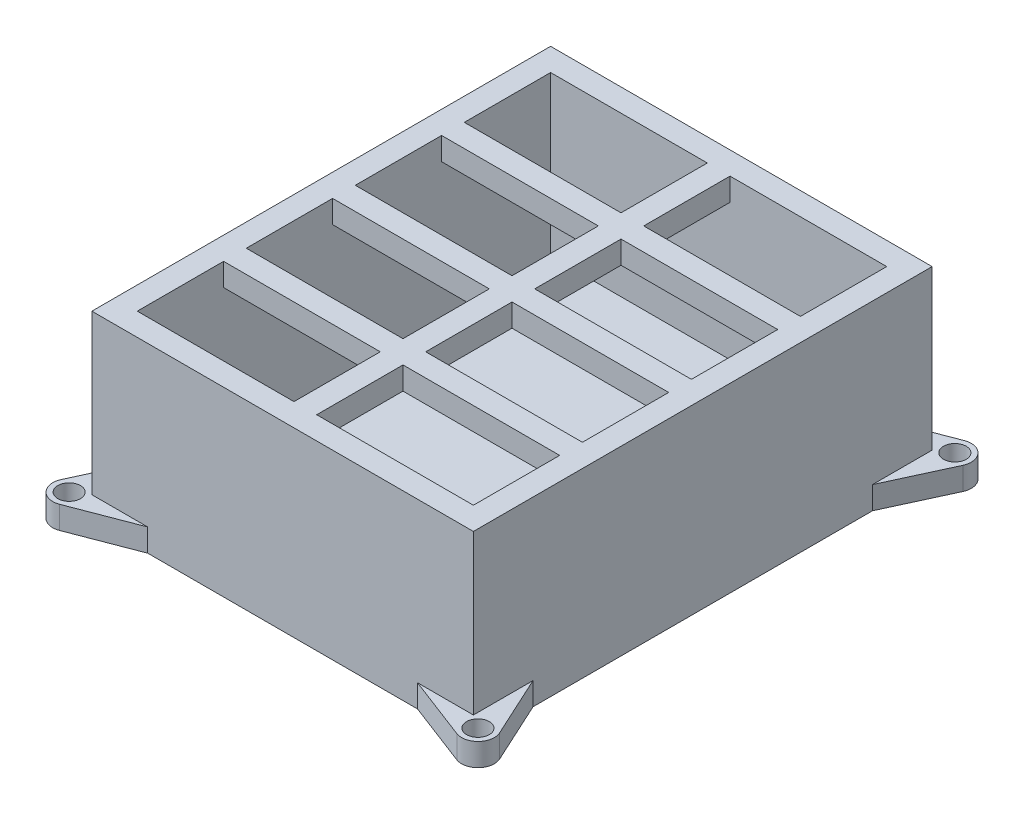
SolidWorks part; units mm, degrees
ref_plane "Front Plane" through (0, 0, 0) normal (0, 0, 1) x (1, 0, 0)
ref_plane "Top Plane" through (0, 0, 0) normal (0, 1, 0) x (1, 0, 0)
ref_plane "Right Plane" through (0, 0, 0) normal (1, 0, 0) x (0, 0, -1)
sketch "Sketch1" plane through (0, 0, 0) normal (0, 1, 0) x (1, 0, 0)
  line L0 (0, 0) -> (0, 10.1) construction
  line L1 (-8.4, -10.1) -> (8.4, -10.1)
  line L2 (-8.4, -10.1) -> (-8.4, 10.1)
  line L3 (-8.4, 10.1) -> (8.4, 10.1)
  line L4 (8.4, -10.1) -> (8.4, 10.1)
  line L5 (-8.4, -10.1) -> (8.4, 10.1) construction
  line L6 (-8.4, 10.1) -> (8.4, -10.1) construction
  line L7 (0, 0) -> (8.4, 0) construction
  line L9 (-7.4, -5.3) -> (-0.5, -5.3)
  line L10 (-7.4, -5.3) -> (-7.4, -9.1)
  line L11 (-7.4, -9.1) -> (-0.5, -9.1)
  line L12 (-0.5, -5.3) -> (-0.5, -9.1)
  line L16 (7.4, -9.1) -> (0.5, -9.1)
  line L17 (0.5, -5.3) -> (0.5, -9.1)
  line L18 (7.4, -5.3) -> (0.5, -5.3)
  line L19 (7.4, -5.3) -> (7.4, -9.1)
  line L20 (-7.4, -0.5) -> (-7.4, -4.3)
  line L21 (-7.4, -0.5) -> (-0.5, -0.5)
  line L22 (-0.5, -0.5) -> (-0.5, -4.3)
  line L23 (-7.4, -4.3) -> (-0.5, -4.3)
  line L24 (7.4, -4.3) -> (0.5, -4.3)
  line L25 (0.5, -0.5) -> (0.5, -4.3)
  line L26 (7.4, -0.5) -> (0.5, -0.5)
  line L27 (7.4, -0.5) -> (7.4, -4.3)
  line L44 (7.4, 0.5) -> (7.4, 4.3)
  line L45 (7.4, 0.5) -> (0.5, 0.5)
  line L46 (0.5, 0.5) -> (0.5, 4.3)
  line L47 (7.4, 4.3) -> (0.5, 4.3)
  line L48 (7.4, 5.3) -> (7.4, 9.1)
  line L49 (7.4, 5.3) -> (0.5, 5.3)
  line L50 (0.5, 5.3) -> (0.5, 9.1)
  line L51 (7.4, 9.1) -> (0.5, 9.1)
  line L52 (-7.4, 9.1) -> (-0.5, 9.1)
  line L53 (-0.5, 5.3) -> (-0.5, 9.1)
  line L54 (-7.4, 5.3) -> (-0.5, 5.3)
  line L55 (-7.4, 5.3) -> (-7.4, 9.1)
  line L56 (-7.4, 0.5) -> (-0.5, 0.5)
  line L57 (-0.5, 0.5) -> (-0.5, 4.3)
  line L58 (-7.4, 4.3) -> (-0.5, 4.3)
  line L59 (-7.4, 0.5) -> (-7.4, 4.3)
  point P0 (0, 0)
  point P43 (-3.95, 9.1)
  dimension "D1" = 6.9
  dimension "D2" = 3.8
  dimension "D4" = 1
  dimension "D5" = 1
  dimension "D6" = 1
  dimension "D7" = 1
  dimension "D8" = 1
  dimension "D3" = 2
extrude "Boss-Extrude1" add sketch "Sketch1" along normal blind 1 contours L1 L4 L3 L2 L51 L48 L49 L50 L47 L44 L45 L46 L23 L20 L21 L22 L9 L12 L11 L10 L18 L19 L16 L17 L26 L27 L24 L25 L54 L55 L52 L53 L56 L59 L58 L57 | L59 L56 L57 L58 | L55 L54 L53 L52 | L48 L51 L50 L49 | L44 L47 L46 L45 | L27 L26 L25 L24 | L20 L23 L22 L21 | L12 L9 L10 L11 | L19 L18 L17 L16 region at (0, 0, 0) region at (-3.95, 0, 7.2) region at (3.95, 0, 7.2) region at (-3.95, 0, 2.4) region at (3.95, 0, 2.4) region at (3.95, 0, -2.4) region at (3.95, 0, -7.2) region at (-3.95, 0, -7.2) region at (-3.95, 0, -2.4)
ref_plane "Plane1" through (0, 7, 0) normal (0, 1, 0) x (1, 0, 0)
sketch "Sketch2" plane through (0, 7, 0) normal (0, 1, 0) x (1, 0, 0)
  line L0 (-7.4, -5.3) -> (-7.4, -9.1) construction
  line L1 (-7.4, -5.3) -> (-0.5, -5.3) construction
  line L2 (-0.5, -5.3) -> (-0.5, -9.1) construction
  line L3 (-7.4, -9.1) -> (-0.5, -9.1) construction
  line L4 (-8.4, -10.1) -> (8.4, -10.1)
  line L6 (-8.4, -10.1) -> (8.4, -10.1)
  line L12 (7.4, -9.1) -> (0.5, -9.1) construction
  line L13 (7.4, -5.3) -> (7.4, -9.1) construction
  line L14 (0.5, -5.3) -> (0.5, -9.1) construction
  line L15 (7.4, -5.3) -> (0.5, -5.3) construction
  line L16 (7.4, -0.5) -> (7.4, -4.3) construction
  line L17 (7.4, -0.5) -> (0.5, -0.5) construction
  line L18 (7.4, -4.3) -> (0.5, -4.3) construction
  line L19 (0.5, -0.5) -> (0.5, -4.3) construction
  line L20 (-0.5, -0.5) -> (-0.5, -4.3) construction
  line L21 (-7.4, -4.3) -> (-0.5, -4.3) construction
  line L22 (-7.4, -0.5) -> (-7.4, -4.3) construction
  line L23 (-7.4, -0.5) -> (-0.5, -0.5) construction
  line L24 (-0.5, 0.5) -> (-0.5, 4.3) construction
  line L25 (-7.4, 4.3) -> (-0.5, 4.3) construction
  line L26 (-7.4, 0.5) -> (-7.4, 4.3) construction
  line L27 (-7.4, 0.5) -> (-0.5, 0.5) construction
  line L28 (7.4, 0.5) -> (7.4, 4.3) construction
  line L29 (7.4, 0.5) -> (0.5, 0.5) construction
  line L30 (0.5, 0.5) -> (0.5, 4.3) construction
  line L31 (7.4, 4.3) -> (0.5, 4.3) construction
  line L32 (7.4, 5.3) -> (7.4, 9.1) construction
  line L33 (7.4, 9.1) -> (0.5, 9.1) construction
  line L34 (7.4, 5.3) -> (0.5, 5.3) construction
  line L35 (0.5, 5.3) -> (0.5, 9.1) construction
  line L36 (-0.5, 5.3) -> (-0.5, 9.1) construction
  line L37 (-7.4, 5.3) -> (-0.5, 5.3) construction
  line L38 (-7.4, 5.3) -> (-7.4, 9.1) construction
  line L39 (-7.4, 9.1) -> (-0.5, 9.1) construction
  line L40 (-7.4, -5.3) -> (-7.4, -9.1)
  line L41 (-7.4, -5.3) -> (-0.5, -5.3)
  line L42 (-0.5, -5.3) -> (-0.5, -9.1)
  line L43 (-7.4, -9.1) -> (-0.5, -9.1)
  line L44 (7.4, -9.1) -> (0.5, -9.1)
  line L45 (7.4, -5.3) -> (7.4, -9.1)
  line L46 (0.5, -5.3) -> (0.5, -9.1)
  line L47 (7.4, -5.3) -> (0.5, -5.3)
  line L48 (7.4, -0.5) -> (7.4, -4.3)
  line L49 (7.4, -0.5) -> (0.5, -0.5)
  line L50 (7.4, -4.3) -> (0.5, -4.3)
  line L51 (0.5, -0.5) -> (0.5, -4.3)
  line L52 (-0.5, -0.5) -> (-0.5, -4.3)
  line L53 (-7.4, -4.3) -> (-0.5, -4.3)
  line L54 (-7.4, -0.5) -> (-7.4, -4.3)
  line L55 (-7.4, -0.5) -> (-0.5, -0.5)
  line L56 (-0.5, 0.5) -> (-0.5, 4.3)
  line L57 (-7.4, 4.3) -> (-0.5, 4.3)
  line L58 (-7.4, 0.5) -> (-7.4, 4.3)
  line L59 (-7.4, 0.5) -> (-0.5, 0.5)
  line L60 (7.4, 0.5) -> (7.4, 4.3)
  line L61 (7.4, 0.5) -> (0.5, 0.5)
  line L62 (0.5, 0.5) -> (0.5, 4.3)
  line L63 (7.4, 4.3) -> (0.5, 4.3)
  line L64 (7.4, 5.3) -> (7.4, 9.1)
  line L65 (7.4, 9.1) -> (0.5, 9.1)
  line L66 (7.4, 5.3) -> (0.5, 5.3)
  line L67 (0.5, 5.3) -> (0.5, 9.1)
  line L68 (-0.5, 5.3) -> (-0.5, 9.1)
  line L69 (-7.4, 5.3) -> (-0.5, 5.3)
  line L70 (-7.4, 5.3) -> (-7.4, 9.1)
  line L71 (-7.4, 9.1) -> (-0.5, 9.1)
  line L76 (8.4, -10.1) -> (8.4, 10.1)
  line L78 (8.4, -10.1) -> (8.4, 10.1)
  line L80 (8.4, 10.1) -> (-8.4, 10.1)
  line L81 (8.4, 10.1) -> (-8.4, 10.1)
  line L82 (-8.4, 10.1) -> (-8.4, -10.1)
  line L83 (-8.4, 10.1) -> (-8.4, -10.1)
  dimension "D1" = 0
extrude "Boss-Extrude2" add sketch "Sketch2" along normal blind 1 separate body
sketch "Sketch4" plane through (0, 1, 0) normal (0, 1, 0) x (1, 0, 0)
  line L4 (-8.4, -10.1) -> (8.4, -10.1)
  line L6 (-8.4, -10.1) -> (8.4, -10.1)
  line L24 (8.4, -10.1) -> (8.4, 10.1)
  line L26 (8.4, -10.1) -> (8.4, 10.1)
  line L40 (8.4, 10.1) -> (-8.4, 10.1)
  line L41 (8.4, 10.1) -> (-8.4, 10.1)
  line L42 (-8.4, 10.1) -> (-8.4, -10.1)
  line L43 (-8.4, 10.1) -> (-8.4, -10.1)
  line L48 (-7.4, 9.1) -> (-7.4, -9.1)
  line L49 (-7.4, -9.1) -> (7.4, -9.1)
  line L50 (7.4, -9.1) -> (7.4, 9.1)
  line L51 (7.4, 9.1) -> (-7.4, 9.1)
  line L52 (-7.4, 9.1) -> (-7.4, -9.1)
  line L53 (-7.4, -9.1) -> (7.4, -9.1)
  line L54 (7.4, -9.1) -> (7.4, 9.1)
  line L55 (7.4, 9.1) -> (-7.4, 9.1)
  dimension "D1" = 0
  dimension "D2" = 1
extrude "Boss-Extrude3" add sketch "Sketch4" along normal up to surface (6 mm away) up to face at (3.95, 7, -7.2)
sketch "Sketch5" plane through (0, 0, 0) normal (0, -1, 0) x (1, 0, 0)
  line L0 (0, 0) -> (0, 5.3631) construction
  line L1 (9.655, 10.1983) -> (8.4, 7.4735)
  line L3 (8.742, 11.1734) -> (5.9406, 10.1)
  line L5 (-9, -10.5) -> (9, -10.5) construction
  line L6 (-9, -10.5) -> (-9, 10.5) construction
  line L17 (-9, 10.5) -> (9, 10.5) construction
  line L18 (9, -10.5) -> (9, 10.5) construction
  line L19 (-9, -10.5) -> (9, 10.5) construction
  line L20 (-9, 10.5) -> (9, -10.5) construction
  line L25 (0, 0) -> (3.0583, 0) construction
  line L30 (-9.655, 10.1983) -> (-8.4, 7.4735)
  line L31 (-8.4, 10.1) -> (-8.4, -10.1) construction
  line L32 (-8.742, 11.1734) -> (-5.9406, 10.1)
  line L33 (-8.4, 10.1) -> (8.4, 10.1) construction
  line L34 (-9.655, -10.1983) -> (-8.4, -7.4735)
  line L35 (-8.742, -11.1734) -> (-5.9406, -10.1)
  line L36 (9.655, -10.1983) -> (8.4, -7.4735)
  line L37 (8.742, -11.1734) -> (5.9406, -10.1)
  line L38 (-5.9406, 10.1) -> (-8.4, 10.1)
  line L39 (-8.4, -7.4735) -> (-8.4, -10.1)
  line L40 (8.4, 7.4735) -> (8.4, 10.1)
  line L41 (5.9406, -10.1) -> (8.4, -10.1)
  line L42 (8.4, 10.1) -> (-8.4, 10.1)
  line L43 (-8.4, 10.1) -> (-8.4, -10.1)
  line L44 (-8.4, -10.1) -> (8.4, -10.1)
  line L45 (8.4, -10.1) -> (8.4, 10.1)
  line L46 (8.4, 10.1) -> (5.9406, 10.1)
  line L47 (-8.4, 10.1) -> (-8.4, 7.4735)
  line L48 (-8.4, -10.1) -> (-5.9406, -10.1)
  line L49 (8.4, -10.1) -> (8.4, -7.4735)
  circle A8 centre (-9, 10.5) radius 0.5
  circle A9 centre (9, 10.5) radius 0.5
  circle A10 centre (9, -10.5) radius 0.5
  circle A11 centre (-9, -10.5) radius 0.5
  arc A12 (-8.5307, 9.9525) -> (-8.4, 10.1) centre (-9, 10.5) ccw
  arc A13 (8.742, 11.1734) -> (9.655, 10.1983) centre (9, 10.5) cw
  arc A14 (-8.5307, -9.9525) -> (-8.4, -10.1) centre (-9, -10.5) cw
  arc A15 (8.742, -11.1734) -> (9.655, -10.1983) centre (9, -10.5) ccw
  arc A16 (-8.742, 11.1734) -> (-9.655, 10.1983) centre (-9, 10.5) ccw
  arc A17 (8.5307, 9.9525) -> (8.4, 10.1) centre (9, 10.5) cw
  arc A18 (8.5307, -9.9525) -> (8.4, -10.1) centre (9, -10.5) ccw
  arc A19 (-8.742, -11.1734) -> (-9.655, -10.1983) centre (-9, -10.5) cw
  point P0 (0, 0)
  line M15 (8.4, 10.1) -> (-8.4, 10.1)
  line M16 (-8.4, 10.1) -> (-8.4, -10.1)
  line M17 (-8.4, -10.1) -> (8.4, -10.1)
  line M18 (8.4, -10.1) -> (8.4, 10.1)
  dimension "D1" = 1
  dimension "D2" = 18
  dimension "D3" = 21
  dimension "D4" = 3
  dimension "D5" = 0
extrude "Boss-Extrude4" add sketch "Sketch5" against normal blind 1 contours A19 L35 L34 A11 M17 M16 | L37 A15 L36 A10 M18 M17 | A13 L3 L1 A9 M15 M18 | L32 A16 L30 A8 M16 M15 region at (8.4127, 0, 9.8969) region at (8.4127, 0, -9.8969) region at (-8.4127, 0, 9.8969) region at (-8.4127, 0, -9.8969)
